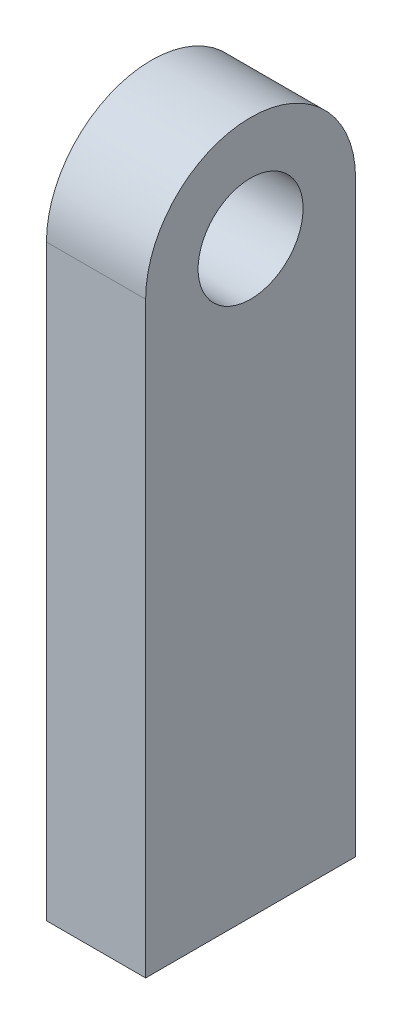
SolidWorks part; units mm, degrees
ref_plane "Front Plane" through (0, 0, 0) normal (0, 0, 1) x (1, 0, 0)
ref_plane "Top Plane" through (0, 0, 0) normal (0, 1, 0) x (1, 0, 0)
ref_plane "Right Plane" through (0, 0, 0) normal (1, 0, 0) x (0, 0, -1)
sketch "Sketch3" plane through (0, 0, 0) normal (1, 0, 0) x (0, 0, -1)
  line L1 (-6.35, 0) -> (6.35, 0)
  line L2 (-6.35, 0) -> (-6.35, -35.56)
  line L3 (-6.35, -35.56) -> (6.35, -35.56)
  line L4 (6.35, 0) -> (6.35, -35.56)
  arc A0 (6.35, 0) -> (-6.35, 0) centre (0, 0) ccw
  circle A1 centre (0, 0) radius 3.175
  point P6 (0, 0)
  point P8 (-0.3854, -2.1785)
  point P9 (-3.8242, -1.1792)
  point P10 (0, 0)
  dimension "D1" = 6.35
  dimension "D2" = 12.7
  dimension "D3" = 35.56
extrude "Boss-Extrude2" add sketch "Sketch3" along normal blind 6 contours A1 L1 L2 L3 L4 | A1 L1 A0 region at (0, 3.317, 0) region at (0, -18.3771, 0)
equation "\"dowel thick\"= 1 / 4"
equation "\"height\"= 1.4"
equation "\"ply thick\"= 6mm"
equation "\"D1@Sketch3\"=\"dowel thick\""
equation "\"D2@Sketch3\"=\"dowel thick\"*2"
equation "\"D3@Sketch3\"=\"height\""
equation "\"D1@Boss-Extrude2\"=\"ply thick\""
